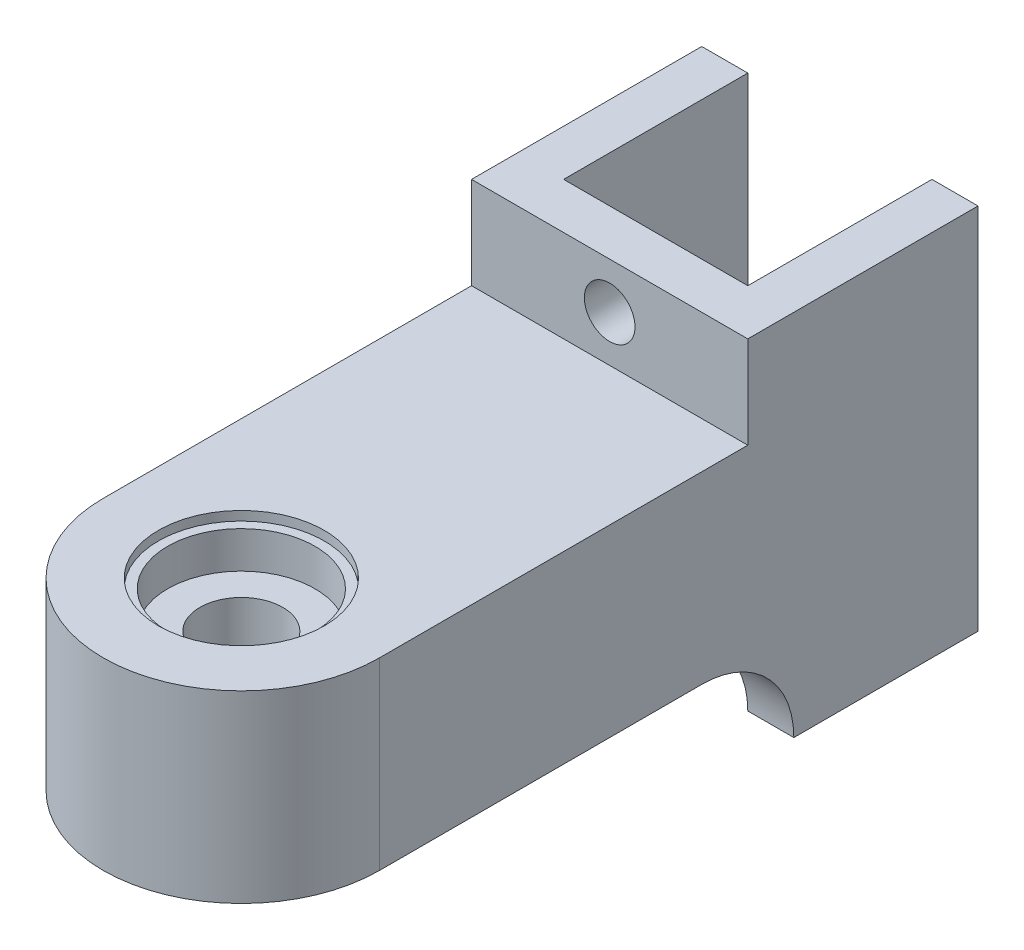
SolidWorks part; units mm, degrees
ref_plane "Front Plane" through (0, 0, 0) normal (0, 0, 1) x (1, 0, 0)
ref_plane "Top Plane" through (0, 0, 0) normal (0, 1, 0) x (1, 0, 0)
ref_plane "Right Plane" through (0, 0, 0) normal (1, 0, 0) x (0, 0, -1)
sketch "Sketch1" plane through (0, 0, 0) normal (0, 1, 0) x (1, 0, 0)
  line L0 (0.5932, -1001.3559) -> (0.5932, -50.8559) construction
  line L1 (-9.4068, -11.3559) -> (10.5932, -11.3559)
  line L2 (-9.4068, -11.3559) -> (-9.4068, 8.6441)
  line L3 (-9.4068, 8.6441) -> (10.5932, 8.6441) construction
  line L4 (10.5932, -11.3559) -> (10.5932, 8.6441)
  line L5 (-9.4068, -11.3559) -> (10.5932, 8.6441) construction
  line L6 (-9.4068, 8.6441) -> (10.5932, -11.3559) construction
  line L7 (-5.4068, -11.3559) -> (6.5932, -11.3559) construction
  line L8 (-5.4068, -11.3559) -> (-5.4068, -19.3559) construction
  line L9 (-5.4068, -19.3559) -> (6.5932, -19.3559) construction
  line L10 (6.5932, -11.3559) -> (6.5932, -19.3559) construction
  line L11 (0.5932, -56.3559) -> (0.5932, -31.8559)
  line L12 (-14.4068, 8.6441) -> (15.5932, 8.6441)
  line L13 (-14.4068, 8.6441) -> (-14.4068, -56.3559)
  line L15 (0.5932, 8.6441) -> (0.5932, -31.8559)
  line L16 (0.5932, -31.8559) -> (0.5932, 48998.6441) construction
  line L17 (15.5932, 8.6441) -> (15.5932, -56.3559)
  line L18 (-14.4068, -16.3559) -> (15.5932, -16.3559)
  circle A0 centre (0.5932, -56.3559) radius 8
  arc A1 (-14.4068, -56.3559) -> (15.5932, -56.3559) centre (0.5932, -56.3559) ccw
  circle A2 centre (0.5932, -56.3559) radius 4.5
  circle A3 centre (0.5932, -56.3559) radius 9
  point P0 (0.5932, -1.3559)
  dimension "D6" = 45
  dimension "D8" = 8
  dimension "D9" = 9
  dimension "D10" = 5
  dimension "D1" = 20
  dimension "D2" = 20
  dimension "D3" = 12
  dimension "D4" = 8
  dimension "D5" = 4
  dimension "D7" = 5
extrude "Boss-Extrude1" add sketch "Sketch1" along normal blind 10 and the other way blind 10 contours L13 A1 L11 A0 L15 L1 L2 L12 | L11 A1 L17 L12 L4 L1 L15 A0 | A3 L18 L13 A1 L17 region at (-9.7639, 0, 6.7131) region at (10.9504, 0, 6.7131) region at (8.0932, 0, 16.9824)
extrude "Boss-Extrude2" add sketch "Sketch1<3>" along normal blind 9 and the other way blind 9 contours L11 A3 A0 | L11 A3 A0 region at (6.7772, 0, 50.172)
sketch "Sketch1<3>" plane through (0, 0, 0) normal (0, 1, 0) x (1, 0, 0) same geometry as "Sketch1"
extrude "Boss-Extrude4" add sketch "Sketch1<4>" along normal blind 5 and the other way blind 5 contours A2 L11 A0 | A2 L11 A0 region at (6.0901, 0, 50.8591)
sketch "Sketch1<4>" plane through (0, 0, 0) normal (0, 1, 0) x (1, 0, 0) same geometry as "Sketch1"
sketch "Sketch2" plane through (0, 10, 0) normal (0, 1, 0) x (1, 0, 0)
  line L1 (10.5932, -11.3559) -> (15.5932, -11.3559)
  line L2 (10.5932, -11.3559) -> (10.5932, 8.6441)
  line L3 (10.5932, 8.6441) -> (15.5932, 8.6441)
  line L4 (15.5932, -11.3559) -> (15.5932, 8.6441)
  line L5 (-9.4068, -11.3559) -> (-14.4068, -11.3559)
  line L6 (-9.4068, -11.3559) -> (-9.4068, 8.6441)
  line L7 (-9.4068, 8.6441) -> (-14.4068, 8.6441)
  line L8 (-14.4068, -11.3559) -> (-14.4068, 8.6441)
extrude "Boss-Extrude3" add sketch "Sketch2" along normal blind 10 and the other way blind 30
sketch "Sketch6" plane through (0, 10, 0) normal (0, 1, 0) x (1, 0, 0)
  line L0 (15.5932, -11.3559) -> (15.5932, -56.3559) construction
  line L1 (-14.4068, -11.3559) -> (15.5932, -11.3559)
  line L2 (-14.4068, -11.3559) -> (-14.4068, -16.3559)
  line L3 (-14.4068, -16.3559) -> (15.5932, -16.3559)
  line L4 (15.5932, -11.3559) -> (15.5932, -16.3559)
  dimension "D1" = 5
extrude "Boss-Extrude6" add sketch "Sketch6" along normal blind 10
fillet "Fillet1" radius 10 2 edges at (-11.9068, -10, 11.3559) (13.0932, -10, 11.3559)
hole_wizard "M5 Clearance Hole1" positions "Sketch7" profile "Sketch8" hole size "M5" standard "ANSI Metric" end condition through all
sketch "Sketch7" plane through (0, 0, 16.3559) normal (0, 0, 1) x (1, 0, 0)
  line L0 (-14.4068, 20) -> (15.5932, 20) construction
  line L1 (15.5932, 20) -> (15.5932, 10) construction
  point P0 (0.5932, 15)
  dimension "D1" = 5
  dimension "D2" = 15
sketch "Sketch8" plane through (0.5932, 15, 16.3559) normal (1, 0, 0) x (0, -1, 0)
  line L0 (0, 0) -> (0, 25)
  line L1 (0, 25) -> (2.75, 25)
  line L2 (2.75, 25) -> (2.75, 0)
  line L5 (2.75, 0) -> (0, 0)
  line L11 (0, -6.35) -> (0, 107.95) construction
  dimension "Thru Hole Dia." = 5.5
  dimension "Thru Hole Depth" = 25
